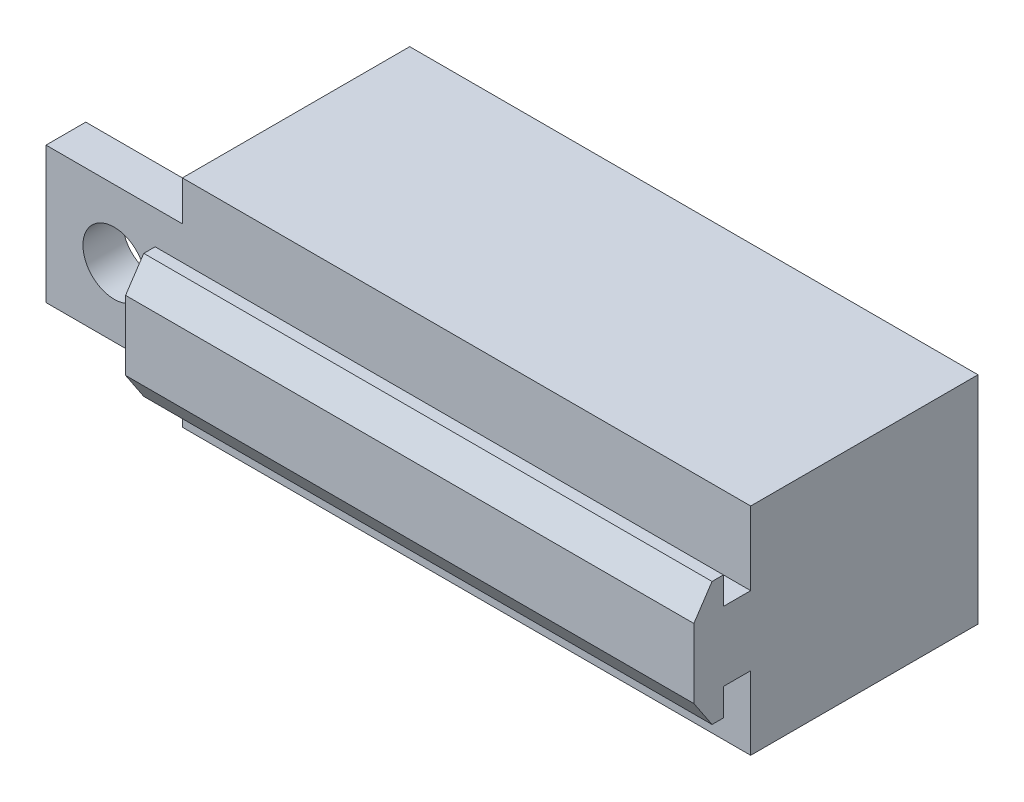
SolidWorks part; units mm, degrees
ref_plane "Front Plane" through (0, 0, 0) normal (0, 0, 1) x (1, 0, 0)
ref_plane "Top Plane" through (0, 0, 0) normal (0, 1, 0) x (1, 0, 0)
ref_plane "Right Plane" through (0, 0, 0) normal (1, 0, 0) x (0, 0, -1)
sketch "Sketch1" plane through (0, 0, 0) normal (0, 1, 0) x (1, 0, 0)
  line L1 (-25, 12.5) -> (25, 12.5)
  line L2 (-25, 12.5) -> (-25, -12.5)
  line L3 (-25, -12.5) -> (25, -12.5)
  line L4 (25, 12.5) -> (25, -12.5)
  line L5 (-25, 12.5) -> (25, -12.5) construction
  line L6 (-25, -12.5) -> (25, 12.5) construction
  point P0 (0, 0)
  dimension "D1" = 50
  dimension "D2" = 25
extrude "Boss-Extrude1" add sketch "Sketch1" along normal blind 19
sketch "Sketch2" plane through (25, 0, 0) normal (1, 0, 0) x (0, 0, -1)
  line L0 (-12.5, 9.5) -> (-7.5, 9.5) construction
  line L1 (-12.5, 19) -> (-12.5, 0) construction
  line L2 (-7.5, 12.55) -> (-7.5, 6.45) construction
  line L3 (-7.5, 12.55) -> (-9.9, 12.55)
  line L4 (-7.5, 6.45) -> (-9.9, 6.45)
  line L5 (-9.9, 12.55) -> (-9.9, 14.95)
  line L6 (-9.9, 14.95) -> (-10.9, 14.95)
  line L7 (-9.9, 6.45) -> (-9.9, 4.05)
  line L8 (-9.9, 4.05) -> (-10.9, 4.05)
  line L9 (-7.5, 12.55) -> (-7.5, 19)
  line L10 (-12.5, 19) -> (12.5, 19) construction
  line L11 (-7.5, 6.45) -> (-7.5, 0)
  line L12 (-12.5, 0) -> (12.5, 0) construction
  line L13 (-9.9, 12.55) -> (-12.5, 12.55) construction
  line L14 (-10.9, 14.95) -> (-12.5, 12.55)
  line L15 (-9.9, 6.45) -> (-12.5, 6.45) construction
  line L16 (-10.9, 4.05) -> (-12.5, 6.45)
  line L17 (-12.5, 6.45) -> (-12.5, 12.55)
  point P7 (-7.5, 9.5)
  point P8 (-12.5, 9.5)
  dimension "D1" = 5
  dimension "D2" = 6.1
  dimension "D3" = 2.4
  dimension "D4" = 2.4
  dimension "D5" = 1
extrude "Cut-Extrude1" cut sketch "Sketch2" along direction (-1, 0, 0) on the side against the normal through all and the other way through all
sketch "Sketch3" plane through (-25, 0, 0) normal (-1, 0, 0) x (0, 0, 1)
  line L6 (7.5, 12.55) -> (7.5, 6.45) construction
  line L7 (7.5, 9.5) -> (5.75, 9.5) construction
  line L8 (7.5, 6.45) -> (7.5, 0) construction
  line L9 (4, 15.5) -> (7.5, 15.5)
  line L10 (4, 15.5) -> (4, 3.5)
  line L11 (4, 3.5) -> (7.5, 3.5)
  line L12 (7.5, 15.5) -> (7.5, 3.5)
  line L13 (4, 15.5) -> (7.5, 3.5) construction
  line L14 (4, 3.5) -> (7.5, 15.5) construction
  dimension "D1" = 12
  dimension "D2" = 3.5
extrude "Boss-Extrude2" add sketch "Sketch3" along normal blind 12
sketch "Sketch4" plane through (0, 0, 4) normal (0, 0, -1) x (-1, 0, 0)
  line L0 (25, 15.5) -> (37, 3.5) construction
  circle A0 centre (31, 9.5) radius 2.75
  dimension "D1" = 5.5
extrude "Cut-Extrude2" cut sketch "Sketch4" against normal up to next contours A0
